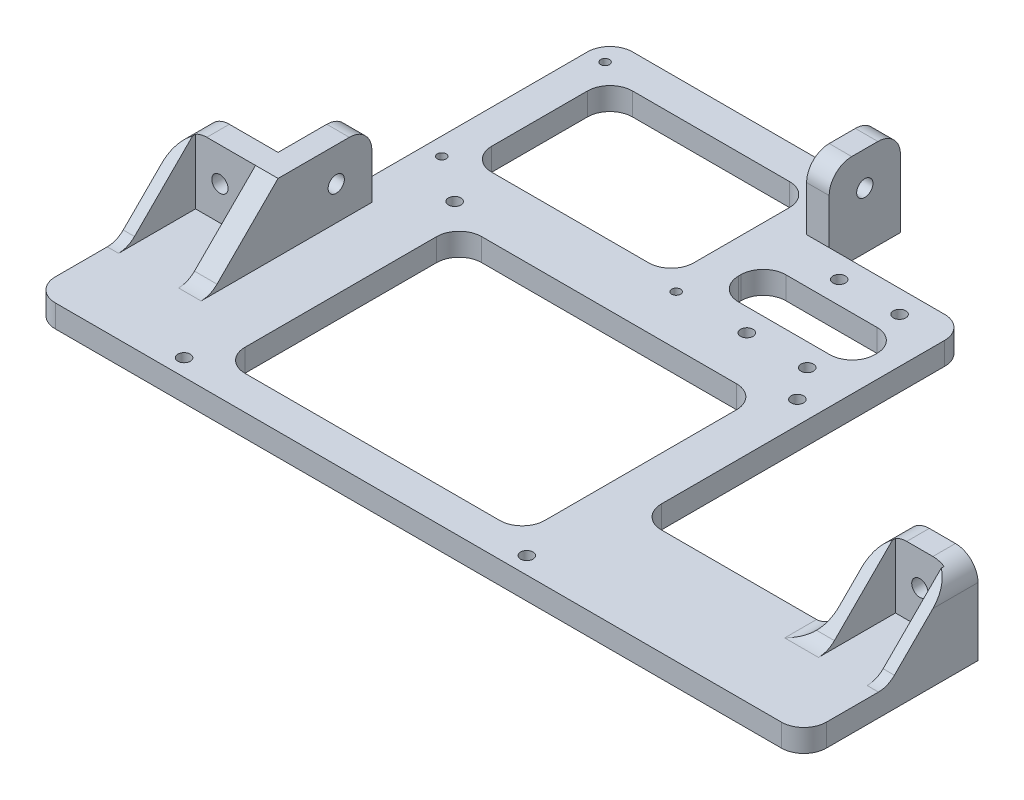
SolidWorks part; units mm, degrees
ref_plane "Front" through (0, 0, 0) normal (0, 0, 1) x (1, 0, 0)
ref_plane "Top" through (0, 0, 0) normal (0, 1, 0) x (1, 0, 0)
ref_plane "Right" through (0, 0, 0) normal (1, 0, 0) x (0, 0, -1)
sketch "Sketch2" plane through (0, 0, 0) normal (0, 1, 0) x (1, 0, 0)
  line L1 (-108.585, 24.511) -> (108.585, 24.511)
  line L2 (-108.585, 24.511) -> (-108.585, -24.511)
  line L3 (-108.585, -24.511) -> (108.585, -24.511)
  line L4 (108.585, 24.511) -> (108.585, -24.511)
  line L5 (-108.585, 24.511) -> (108.585, -24.511) construction
  line L6 (-108.585, -24.511) -> (108.585, 24.511) construction
  point P0 (0, 0)
  dimension "D1" = 217.17
  dimension "D2" = 49.022
extrude "Boss-Extrude1" add sketch "Sketch2" along normal blind 6.35
sketch "Sketch3" plane through (0, 0, 0) normal (0, -1, 0) x (1, 0, 0)
  line L1 (108.585, -24.511) -> (88.519, -24.511)
  line L2 (108.585, -24.511) -> (108.585, -18.161)
  line L3 (108.585, -18.161) -> (88.519, -18.161)
  line L4 (88.519, -24.511) -> (88.519, -18.161)
  line L5 (-108.585, -24.511) -> (-88.519, -24.511)
  line L6 (-108.585, -24.511) -> (-108.585, -18.161)
  line L7 (-108.585, -18.161) -> (-88.519, -18.161)
  line L8 (-88.519, -24.511) -> (-88.519, -18.161)
  dimension "D1" = 6.35
  dimension "D2" = 20.066
extrude "Boss-Extrude2" add sketch "Sketch3" against normal blind 25.4
sketch "Sketch5" plane through (0, 6.35, 0) normal (0, 1, 0) x (1, 0, 0)
  line L1 (-88.519, 24.511) -> (32.131, 24.511)
  line L2 (-88.519, 24.511) -> (-88.519, 97.917)
  line L3 (-88.519, 97.917) -> (32.131, 97.917)
  line L4 (32.131, 24.511) -> (32.131, 97.917)
  dimension "D1" = 120.65
  dimension "D2" = 73.406
extrude "Boss-Extrude3" add sketch "Sketch5" against normal up to surface (6.35 mm away) contours L2 L3 L4 L1 up to face at (0, 0, 0)
sketch "Sketch6" plane through (0, 6.35, 0) normal (0, 1, 0) x (1, 0, 0)
  line L0 (-88.519, 24.511) -> (-88.519, 18.161) construction
  line L1 (-88.519, 18.161) -> (-82.169, 18.161)
  line L2 (-88.519, 18.161) -> (-88.519, 44.577)
  line L3 (-88.519, 44.577) -> (-82.169, 44.577)
  line L4 (-82.169, 18.161) -> (-82.169, 44.577)
  dimension "D1" = 20.066
extrude "Boss-Extrude4" add sketch "Sketch6" along normal up to surface (19.05 mm away) up to face at (-98.552, 25.4, -21.336)
sketch "Sketch7" plane through (0, 0, -24.511) normal (0, 0, -1) x (-1, 0, 0)
  line L0 (-88.519, 15.875) -> (-108.585, 15.875) construction
  line L1 (-88.519, 25.4) -> (-88.519, 6.35) construction
  line L2 (-108.585, 25.4) -> (-108.585, 0) construction
  line L3 (108.585, 15.875) -> (88.519, 15.875) construction
  line L4 (108.585, 25.4) -> (108.585, 0) construction
  line L5 (88.519, 25.4) -> (88.519, 0) construction
  circle A0 centre (-98.552, 15.875) radius 2.286
  circle A1 centre (98.552, 15.875) radius 2.286
  dimension "D1" = 4.572
extrude "Cut-Extrude1" cut sketch "Sketch7" against normal through all
sketch "Sketch8" plane through (-88.519, 0, 0) normal (-1, 0, 0) x (0, 0, 1)
  line L0 (-44.577, 15.875) -> (-24.511, 15.875) construction
  line L1 (-44.577, 25.4) -> (-44.577, 6.35) construction
  line L2 (-24.511, 25.4) -> (-24.511, 0) construction
  circle A0 centre (-34.544, 15.875) radius 2.286
  dimension "D1" = 4.572
extrude "Cut-Extrude2" cut sketch "Sketch8" against normal through all
sketch "Sketch9" plane through (0, 6.35, 0) normal (0, 1, 0) x (1, 0, 0)
  line L1 (88.519, 24.511) -> (32.131, 24.511)
  line L2 (88.519, 24.511) -> (88.519, 5.461)
  line L3 (88.519, 5.461) -> (32.131, 5.461)
  line L4 (32.131, 24.511) -> (32.131, 5.461)
  point P5 (32.131, 24.511)
  dimension "D1" = 19.05
extrude "Cut-Extrude3" cut sketch "Sketch9" against normal through all
sketch "Sketch11" plane through (0, 6.35, 0) normal (0, 1, 0) x (1, 0, 0)
  line L1 (-88.519, 97.917) -> (-6.731, 97.917)
  line L2 (-88.519, 97.917) -> (-88.519, 117.983)
  line L3 (-88.519, 117.983) -> (-6.731, 117.983)
  line L4 (-6.731, 97.917) -> (-6.731, 117.983)
  dimension "D1" = 81.788
  dimension "D2" = 20.066
extrude "Boss-Extrude5" add sketch "Sketch11" against normal up to surface (6.35 mm away) up to face at (6.4262, 0, -25.5778)
sketch "Sketch12" plane through (0, 0, 0) normal (0, -1, 0) x (1, 0, 0)
  line L0 (-88.519, -117.983) -> (-6.731, -117.983) construction
  line L1 (-6.731, -97.917) -> (-13.081, -97.917)
  line L2 (-6.731, -97.917) -> (-6.731, -117.983)
  line L3 (-6.731, -117.983) -> (-13.081, -117.983)
  line L4 (-13.081, -97.917) -> (-13.081, -117.983)
  dimension "D1" = 6.35
extrude "Boss-Extrude6" add sketch "Sketch12" against normal blind 25.4
sketch "Sketch16" plane through (0, 6.35, 0) normal (0, 1, 0) x (1, 0, 0)
  line L1 (-83.5494, 111.633) -> (-17.5494, 111.633) construction
  line L2 (-83.5494, 111.633) -> (-83.5494, 65.633) construction
  line L3 (-83.5494, 65.633) -> (-17.5494, 65.633) construction
  line L4 (-17.5494, 111.633) -> (-17.5494, 65.633) construction
  line L5 (-83.5494, 111.633) -> (-17.5494, 65.633) construction
  line L6 (-83.5494, 65.633) -> (-17.5494, 111.633) construction
  line L7 (-70.739, 56.4515) -> (25.781, 56.4515) construction
  line L8 (-70.739, 56.4515) -> (-70.739, -19.7485) construction
  line L9 (-70.739, -19.7485) -> (25.781, -19.7485) construction
  line L10 (25.781, 56.4515) -> (25.781, -19.7485) construction
  line L11 (-70.739, 56.4515) -> (25.781, -19.7485) construction
  line L12 (-70.739, -19.7485) -> (25.781, 56.4515) construction
  line L13 (-13.081, 117.983) -> (-88.519, 117.983) construction
  line L14 (-108.585, -24.511) -> (108.585, -24.511) construction
  line L15 (32.131, 5.461) -> (32.131, 97.917) construction
  line L17 (-78.994, 108.458) -> (-22.1049, 108.458)
  line L18 (-78.994, 108.458) -> (-78.994, 68.808)
  line L19 (-78.994, 68.808) -> (-22.1049, 68.808)
  line L20 (-22.1049, 108.458) -> (-22.1049, 68.808)
  line L21 (-78.994, 108.458) -> (-22.1049, 68.808) construction
  line L22 (-78.994, 68.808) -> (-22.1049, 108.458) construction
  line L23 (-64.7065, 51.689) -> (19.7485, 51.689)
  line L24 (-64.7065, 51.689) -> (-64.7065, -14.986)
  line L25 (-64.7065, -14.986) -> (19.7485, -14.986)
  line L26 (19.7485, 51.689) -> (19.7485, -14.986)
  line L27 (-64.7065, 51.689) -> (19.7485, -14.986) construction
  line L28 (-64.7065, -14.986) -> (19.7485, 51.689) construction
  line L29 (2.431, 91.567) -> (19.431, 91.567) construction
  line L30 (2.431, 91.567) -> (2.431, 65.567) construction
  line L31 (2.431, 65.567) -> (19.431, 65.567) construction
  line L32 (19.431, 91.567) -> (19.431, 65.567) construction
  line L33 (2.431, 91.567) -> (19.431, 65.567) construction
  line L34 (2.431, 65.567) -> (19.431, 91.567) construction
  line L35 (9.942, 78.567) -> (-49990.058, 78.567) construction
  line L36 (-6.731, 97.917) -> (32.131, 97.917) construction
  line L37 (-12.5799, 85.217) -> (25.781, 85.217)
  line L38 (-12.5799, 85.217) -> (-12.5799, 71.917)
  line L39 (-12.5799, 71.917) -> (25.781, 71.917)
  line L40 (25.781, 85.217) -> (25.781, 71.917)
  line L41 (-12.5799, 85.217) -> (25.781, 71.917) construction
  line L42 (-12.5799, 71.917) -> (25.781, 85.217) construction
  line L43 (-6.731, 97.917) -> (32.131, 97.917) construction
  line L45 (-88.519, 44.577) -> (-88.519, 117.983) construction
  circle A0 centre (-17.5494, 111.633) radius 1.25
  circle A1 centre (-17.5494, 65.633) radius 1.25
  circle A2 centre (-83.5494, 65.633) radius 1.25
  circle A3 centre (-83.5494, 111.633) radius 1.25
  circle A4 centre (-70.739, 56.4515) radius 1.75
  circle A5 centre (-70.739, -19.7485) radius 1.75
  circle A6 centre (25.781, -19.7485) radius 1.75
  circle A7 centre (25.781, 56.4515) radius 1.75
  circle A8 centre (19.431, 91.567) radius 1.75
  circle A9 centre (19.431, 65.567) radius 1.75
  circle A10 centre (2.431, 65.567) radius 1.75
  circle A11 centre (2.431, 91.567) radius 1.75
  point P0 (-50.5494, 88.633)
  point P5 (-22.479, 18.3515)
  point P25 (-50.5494, 88.633)
  point P27 (-22.479, 18.3515)
  point P36 (10.931, 78.567)
  point P49 (6.6006, 78.567)
  dimension "D9" = 2.5
  dimension "D10" = 3.5
  dimension "D1" = 46
  dimension "D2" = 66
  dimension "D3" = 12.7
  dimension "D4" = 6.35
  dimension "D5" = 4.7625
  dimension "D6" = 76.2
  dimension "D7" = 96.52
  dimension "D8" = 6.35
  dimension "D11" = 9.525
  dimension "D12" = 9.525
  dimension "D13" = 17
  dimension "D14" = 26
  dimension "D15" = 6.35
  dimension "D16" = 12.7
  dimension "D17" = 9.525
  dimension "D18" = 6.35
  dimension "D19" = 9.525
extrude "Cut-Extrude6" cut sketch "Sketch16" against normal through all
sketch "Sketch17" plane through (-108.585, 0, 0) normal (-1, 0, 0) x (0, 0, 1)
  line L0 (-18.161, 25.4) -> (-18.161, 6.35)
  line L1 (-18.161, 6.35) -> (0.889, 6.35)
  line L2 (-18.161, 6.35) -> (24.511, 6.35) construction
  line L3 (0.889, 6.35) -> (-18.161, 25.4)
extrude "Boss-Extrude8" add sketch "Sketch17" against normal blind 3.175
sketch "Sketch18" plane through (108.585, 0, 0) normal (1, 0, 0) x (0, 0, -1)
  line L3 (18.161, 25.4) -> (-0.889, 6.35)
  line L4 (-0.889, 6.35) -> (18.161, 6.35)
  line L5 (18.161, 6.35) -> (18.161, 25.4)
  line L6 (18.161, 25.4) -> (-0.889, 6.35)
  line L7 (-0.889, 6.35) -> (18.161, 6.35)
  line L8 (18.161, 6.35) -> (18.161, 25.4)
  dimension "D1" = 0
extrude "Boss-Extrude9" add sketch "Sketch18" against normal blind 3.175
sketch "Sketch19" plane through (88.519, 0, 0) normal (-1, 0, 0) x (0, 0, 1)
  line L3 (-18.161, 25.4) -> (-18.161, 6.35)
  line L4 (-18.161, 6.35) -> (0.889, 6.35)
  line L5 (0.889, 6.35) -> (-18.161, 25.4)
  line L6 (-18.161, 25.4) -> (-18.161, 6.35)
  line L7 (-18.161, 6.35) -> (0.889, 6.35)
  line L8 (0.889, 6.35) -> (-18.161, 25.4)
  dimension "D1" = 0
extrude "Boss-Extrude10" add sketch "Sketch19" against normal blind 3.175
sketch "Sketch20" plane through (-82.169, 0, 0) normal (1, 0, 0) x (0, 0, -1)
  line L3 (18.161, 25.4) -> (-0.889, 6.35)
  line L4 (-0.889, 6.35) -> (18.161, 6.35)
  line L5 (18.161, 6.35) -> (18.161, 25.4)
  line L6 (18.161, 25.4) -> (-0.889, 6.35)
  line L7 (-0.889, 6.35) -> (18.161, 6.35)
  line L8 (18.161, 6.35) -> (18.161, 25.4)
  dimension "D1" = 0
extrude "Boss-Extrude11" add sketch "Sketch20" against normal blind 6.35
fillet "Fillet1" radius 6.35 18 edges at (88.519, 3.175, -5.461) (32.131, 3.175, -5.461) (32.131, 3.175, -97.917) (-108.585, 3.175, 24.511) (108.585, 3.175, 24.511) (25.781, 3.175, -71.917) (25.781, 3.175, -85.217) (-12.5799, 3.175, -85.217) (-12.5799, 3.175, -71.917) (-64.7065, 3.175, 14.986) (19.7485, 3.175, 14.986) (19.7485, 3.175, -51.689) (-64.7065, 3.175, -51.689) (-78.994, 3.175, -108.458) (-78.994, 3.175, -68.808) (-22.1049, 3.175, -68.808) (-22.1049, 3.175, -108.458) (-88.519, 3.175, -117.983)
sketch "Sketch21" plane through (-13.081, 0, 0) normal (-1, 0, 0) x (0, 0, 1)
  line L0 (-117.983, 15.875) -> (-97.917, 15.875) construction
  line L1 (-117.983, 25.4) -> (-117.983, 6.35) construction
  line L2 (-97.917, 25.4) -> (-97.917, 6.35) construction
  circle A0 centre (-107.95, 15.875) radius 2.286
  dimension "D1" = 4.572
extrude "Cut-Extrude7" cut sketch "Sketch21" against normal through all
fillet "Fillet2" radius 6.35 11 edges at (88.519, 6.35, -5.461) (106.9975, 6.35, 0.889) (108.585, 25.4, -21.336) (88.519, 25.4, -21.336) (90.1065, 6.35, 0.889) (-9.906, 25.4, -117.983) (-85.344, 25.4, -44.577) (-108.585, 25.4, -21.336) (-85.344, 6.35, 0.889) (-106.9975, 6.35, 0.889) (-9.906, 25.4, -97.917)
